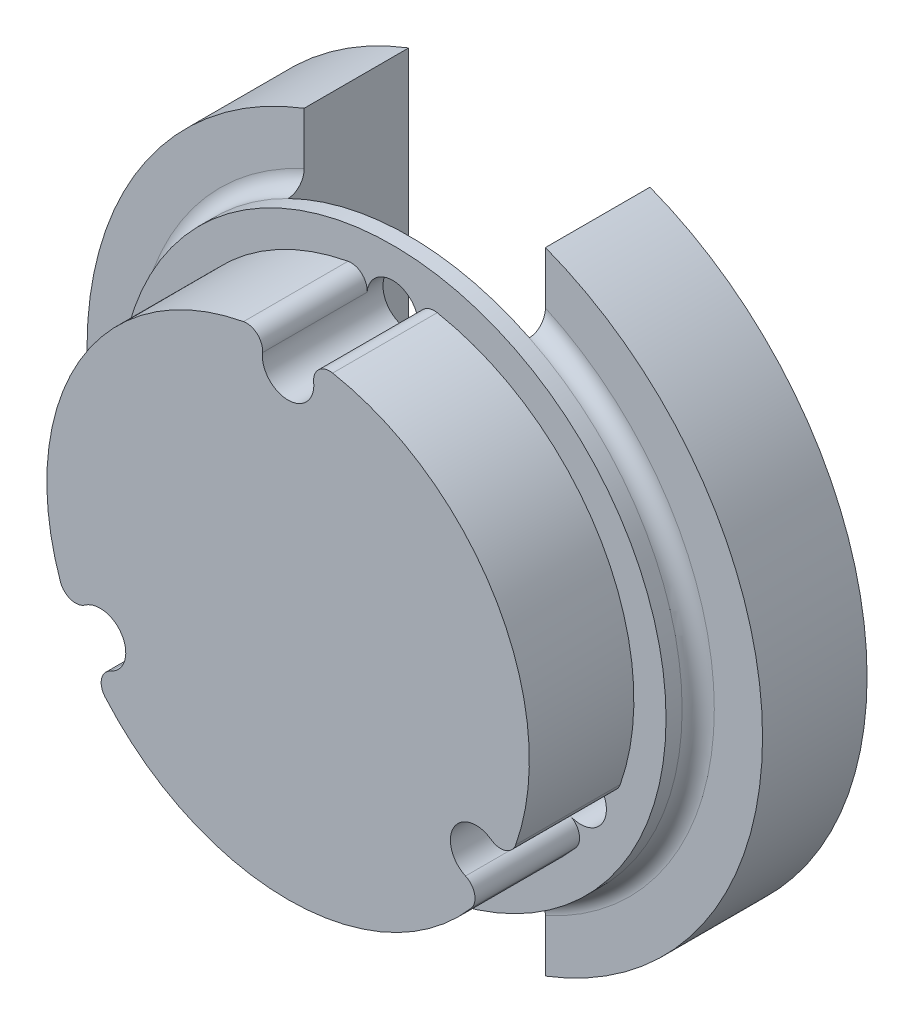
SolidWorks part; units mm, degrees
material "ABS"
ref_plane "前视基准面" through (0, 0, 0) normal (0, 0, 1) x (1, 0, 0)
ref_plane "上视基准面" through (0, 0, 0) normal (0, 1, 0) x (1, 0, 0)
ref_plane "右视基准面" through (0, 0, 0) normal (1, 0, 0) x (0, 0, -1)
sketch "草图1" plane through (0, 0, 0) normal (0, 0, 1) x (1, 0, 0)
  circle A0 centre (0, 0) radius 15
  dimension "D1" = 30
extrude "凸台-拉伸1" add sketch "草图1" along normal blind 6.5
sketch "草图2" plane through (0, 0, 0) normal (0, 0, -1) x (-1, 0, 0)
  circle A0 centre (0, 0) radius 21
  dimension "D1" = 42
extrude "凸台-拉伸2" add sketch "草图2" along normal blind 8.5
sketch "草图3" plane through (0, 0, -8.5) normal (0, 0, -1) x (-1, 0, 0)
  circle A0 centre (0, 0) radius 13.5 construction
  circle A1 centre (0, 13.5) radius 1.6
  circle A2 centre (11.6913, -6.75) radius 1.6
  circle A3 centre (-11.6913, -6.75) radius 1.6
  point P11 (0, 0)
  dimension "D1" = 27
  dimension "D2" = 3.2
  dimension "D3" = 3
extrude "切除-拉伸1" cut sketch "草图3" against normal blind 26.5
sketch "草图6" plane through (0, 0, -8.5) normal (0, 0, -1) x (-1, 0, 0)
  line L1 (-7.5, -25) -> (7.5, -25)
  line L2 (-7.5, -25) -> (-7.5, 25)
  line L3 (-7.5, 25) -> (7.5, 25)
  line L4 (7.5, -25) -> (7.5, 25)
  line L5 (-7.5, -25) -> (7.5, 25) construction
  line L6 (-7.5, 25) -> (7.5, -25) construction
  point P0 (0, 0)
  dimension "D1" = 15
  dimension "D2" = 50
extrude "切除-拉伸3" cut sketch "草图6" against normal blind 7.5
fillet "圆角1" radius 1 6 edges at (-12.687, -8.0024, 3.25) (-13.2738, -6.9861, 3.25) (12.687, -8.0024, 3.25) (13.2738, -6.9861, 3.25) (-0.5868, 14.9885, 3.25) (0.5868, 14.9885, 3.25)
sketch "草图7" plane through (0, 0, 0) normal (0, 0, 1) x (1, 0, 0)
  circle A0 centre (0, 0) radius 17
  circle A1 centre (0, 0) radius 21
  circle A2 centre (0, 0) radius 21
  arc A3 (14.1526, -4.9703) -> (2.7719, 14.7417) centre (0, 0) ccw construction
  dimension "D2" = 2
  dimension "D1" = 0
extrude "切除-拉伸4" cut sketch "草图7" against normal blind 2
fillet "圆角2" radius 1 2 edges at (-17, 0, -2) (17, 0, -2)
